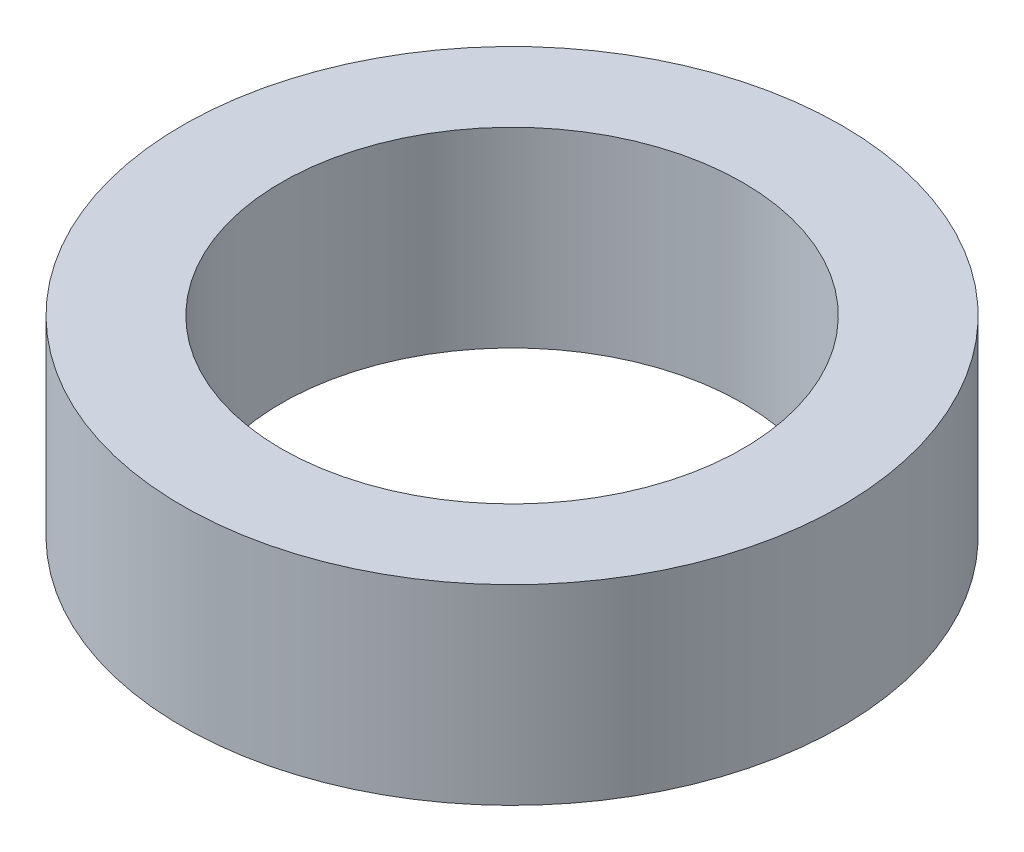
SolidWorks part; units mm, degrees
ref_plane "Front Plane" through (0, 0, 0) normal (0, 0, 1) x (1, 0, 0)
ref_plane "Top Plane" through (0, 0, 0) normal (0, 1, 0) x (1, 0, 0)
ref_plane "Right Plane" through (0, 0, 0) normal (1, 0, 0) x (0, 0, -1)
sketch "Sketch1" plane through (0, 0, 0) normal (0, 1, 0) x (1, 0, 0)
  circle A0 centre (0, 0) radius 50
  dimension "FLANGE_OD" = 100
extrude "Boss-Extrude1" add sketch "Sketch1" along normal blind 29
sketch "Sketch2" plane through (0, 0, 0) normal (0, 1, 0) x (1, 0, 0)
  circle A0 centre (0, 0) radius 35
  dimension "BORE_D" = 70
extrude "Cut-Extrude1" cut sketch "Sketch2" along normal through all
sketch "Sketch3" plane through (0, 29, 0) normal (0, 1, 0) x (1, 0, 0)
  circle A0 centre (0, 0) radius 22.6802 construction
  circle A1 centre (-22.6802, 0) radius 2.4328
  dimension "BOLT_D" = 4.8656
  dimension "BOLT_PCD" = 45.3605
extrude "Cut-Extrude2" cut sketch "Sketch3" against normal blind 20.301 rebuild error yes
pattern_circular "CirPattern1" count 6 over 360 rebuild error yes
